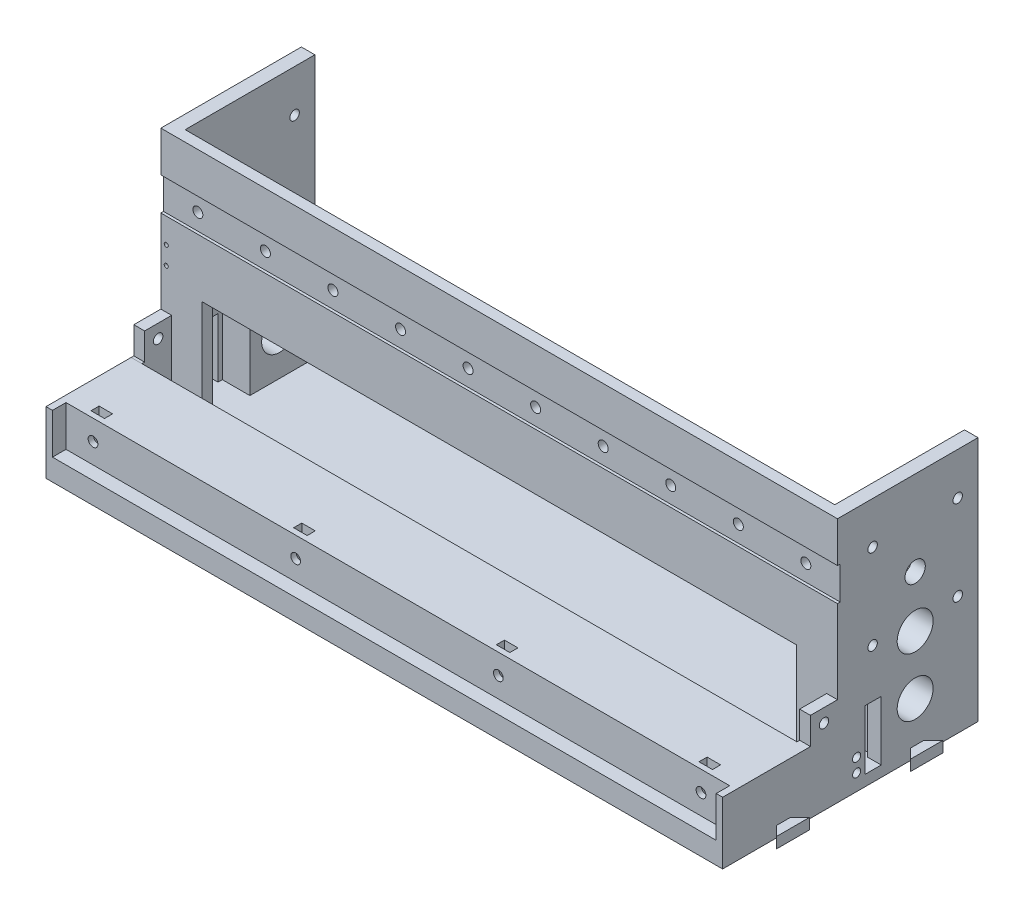
SolidWorks part; units mm, degrees
ref_plane "Front Plane" through (0, 0, 0) normal (0, 0, 1) x (1, 0, 0)
ref_plane "Top Plane" through (0, 0, 0) normal (0, 1, 0) x (1, 0, 0)
ref_plane "Right Plane" through (0, 0, 0) normal (1, 0, 0) x (0, 0, -1)
sketch "Sketch21" plane through (0, 0, 0) normal (0, 1, 0) x (1, 0, 0)
  line L1 (0, 0) -> (250.4, 0)
  line L2 (0, 0) -> (0, -94.5)
  line L3 (0, -94.5) -> (250.4, -94.5)
  line L4 (250.4, 0) -> (250.4, -94.5)
  dimension "D1" = 250.4
  dimension "D2" = 94.5
extrude "Base" add sketch "Sketch21" along normal blind 4
sketch "Sketch22" plane through (0, 4, 0) normal (0, 1, 0) x (1, 0, 0)
  line L1 (0, -52) -> (250.4, -52)
  line L2 (0, -52) -> (0, -48)
  line L3 (0, -48) -> (250.4, -48)
  line L4 (250.4, -52) -> (250.4, -48)
  line L7 (250.4, 0) -> (0, 0) construction
  dimension "D1" = 4
  dimension "D2" = 48
extrude "MainWall" add sketch "Sketch22" along normal blind 87
ref_plane "MiddlePlane" through (125.2, 0, 0) normal (-1, 0, 0) x (0, 0, 1)
sketch "Sketch2" plane through (0, 0, 52) normal (0, 0, 1) x (1, 0, 0)
  line L0 (0, 91) -> (0, 4) construction
  line L1 (250.4, 76) -> (0, 76)
  line L2 (250.4, 76) -> (250.4, 63.8)
  line L3 (250.4, 63.8) -> (0, 63.8)
  line L4 (0, 76) -> (0, 63.8)
  line L5 (0, 91) -> (250.4, 91) construction
  line L6 (250.4, 91) -> (250.4, 4) construction
  dimension "D1" = 12.2
  dimension "D3" = 15
extrude "RailCutout" cut sketch "Sketch2" against normal blind 1
sketch "Sketch6" plane through (0, 0, 52) normal (0, 0, 1) x (1, 0, 0)
  line L0 (0, 63.8) -> (250.4, 63.8) construction
  line L1 (235.2, 23) -> (15.2, 23)
  line L2 (235.2, 23) -> (235.2, 43)
  line L3 (235.2, 43) -> (15.2, 43)
  line L5 (125.2, 63.8) -> (125.2, 43) construction
  line L6 (0, 4) -> (250.4, 4) construction
  line L9 (15.2, 43) -> (15.2, 23)
  dimension "D1" = 20
  dimension "D2" = 19
  dimension "D3" = 220
extrude "PaperChannel" cut sketch "Sketch6" against normal blind 5
sketch "Sketch3" plane through (0, 0, 51) normal (0, 0, 1) x (1, 0, 0)
  line L1 (250.4, 63.8) -> (250.4, 76) construction
  line L3 (237.7, 69.9) -> (250.4, 69.9) construction
  circle A0 centre (237.7, 69.9) radius 1.85
  dimension "D1" = 12.7
  dimension "D2" = 3.7
extrude "RailScrewHole" cut sketch "Sketch3" against normal blind 4
pattern_linear "RailScrewPattern" count 10 spacing 25 along (-1, 0, 0) of "RailScrewHole"
sketch "Sketch13" plane through (0, 0, 0) normal (1, 0, 0) x (0, 0, -1)
  line L0 (0, 4) -> (0, 0) construction
  line L1 (-48, 91) -> (0, 91)
  line L2 (-48, 91) -> (-48, 4)
  line L3 (-48, 4) -> (0, 4)
  line L4 (0, 91) -> (0, 4)
  line L6 (-48, 91) -> (-48, 4) construction
  line L7 (0, 4) -> (-48, 4) construction
  dimension "D2" = 87
extrude "YWall" add sketch "Sketch13" along normal blind 5
sketch "Sketch20" plane through (0, 4, 0) normal (0, 1, 0) x (1, 0, 0)
  line L0 (250.4, -94.5) -> (250.4, -52) construction
  line L1 (250.4, -52) -> (0, -52)
  line L2 (250.4, -52) -> (250.4, -94.5)
  line L3 (250.4, -94.5) -> (0, -94.5)
  line L4 (0, -52) -> (0, -94.5)
  line L5 (0, -52) -> (0, -94.5) construction
  line L8 (0, -52) -> (250.4, -52) construction
  dimension "D2" = 42.5
extrude "BaseExtension" add sketch "Sketch20" along normal blind 19
sketch "Sketch14" plane through (0, 0, 0) normal (1, 0, 0) x (0, 0, -1)
  line L0 (-23.25, 40.65) -> (-23.25, 19) construction
  line L1 (-48, 4) -> (0, 4) construction
  line L2 (-23.25, 40.65) -> (-23.25, 59.65) construction
  line L3 (-39, 75.4) -> (-7.5, 75.4) construction
  line L4 (-39, 75.4) -> (-7.5, 43.9) construction
  line L5 (-7.5, 75.4) -> (-39, 43.9) construction
  line L6 (-39, 43.9) -> (-7.5, 43.9) construction
  line L7 (-48, 91) -> (-48, 4) construction
  circle A0 centre (-23.25, 19) radius 6.65
  circle A1 centre (-23.25, 40.65) radius 6.65
  circle A2 centre (-23.25, 59.65) radius 3.75
  circle A3 centre (-7.5, 43.9) radius 1.75
  circle A4 centre (-7.5, 75.4) radius 1.75
  circle A5 centre (-39, 75.4) radius 1.75
  circle A6 centre (-39, 43.9) radius 1.75
  point P18 (-23.25, 59.65)
  dimension "D1" = 21.65
  dimension "D2" = 13.3
  dimension "D3" = 13.3
  dimension "D6" = 7.5
  dimension "D7" = 3.5
  dimension "D8" = 3.5
  dimension "D9" = 3.5
  dimension "D10" = 3.5
  dimension "D15" = 15
  dimension "D4" = 9
  dimension "D5" = 19
  dimension "D11" = 31.5
  dimension "D12" = 31.5
  dimension "D13" = 31.5
  dimension "D14" = 31.5
extrude "MotorScrewBearingHoles" cut sketch "Sketch14" along normal blind 5
mirror "MirrorYWallHoles" about plane through (125.2, 0, 0) normal (-1, 0, 0) of "MotorScrewBearingHoles", "YWall"
sketch "Sketch26" plane through (5, 0, 0) normal (1, 0, 0) x (0, 0, -1)
  line L0 (-23.25, 50.65) -> (-23.25, 4) construction
  line L1 (-34.25, 4) -> (-12.25, 4)
  line L2 (-34.25, 4) -> (-34.25, 43.15)
  line L3 (-26.75, 50.65) -> (-19.75, 50.65)
  line L4 (-12.25, 4) -> (-12.25, 43.15)
  line L6 (-48, 4) -> (0, 4) construction
  circle A0 centre (-23.25, 19) radius 6.65
  circle A1 centre (-23.25, 40.65) radius 6.65
  arc A2 (-34.25, 43.15) -> (-26.75, 50.65) centre (-26.75, 43.15) cw
  arc A3 (-19.75, 50.65) -> (-12.25, 43.15) centre (-19.75, 43.15) cw
  dimension "D1" = 10
  dimension "D2" = 7.5
  dimension "D3" = 22
extrude "LeftRollerOffset" add sketch "Sketch26" along normal blind 10.2
chamfer "Chamfer2" distance 15 angle 45 1 edges at (125.2, 23, 48)
sketch "Sketch28" plane through (245.4, 0, 0) normal (-1, 0, 0) x (0, 0, 1)
  line L0 (48, 4) -> (0, 4) construction
  line L1 (19.75, 50.65) -> (26.75, 50.65)
  line L2 (12.25, 43.15) -> (12.25, 4)
  line L3 (12.25, 4) -> (34.25, 4)
  line L4 (34.25, 43.15) -> (34.25, 4)
  line L5 (23.25, 4) -> (23.25, 50.65) construction
  circle A0 centre (23.25, 40.65) radius 6.65
  circle A2 centre (23.25, 19) radius 6.65
  arc A3 (19.75, 50.65) -> (12.25, 43.15) centre (19.75, 43.15) ccw
  arc A4 (26.75, 50.65) -> (34.25, 43.15) centre (26.75, 43.15) cw
  dimension "D1" = 10
  dimension "D3" = 7.5
  dimension "D2" = 22
extrude "RightRollerOffset" add sketch "Sketch28" along normal blind 10
sketch "Sketch29" plane through (0, 0, 0) normal (-1, 0, 0) x (0, 0, 1)
  line L0 (52, 23) -> (52, 33)
  line L1 (52, 63.8) -> (52, 12) construction
  line L3 (63, 23) -> (94.5, 23) construction
  line L5 (52, 33) -> (62, 33)
  line L6 (62, 33) -> (62, 23)
  line L7 (52, 33) -> (62, 23) construction
  line L8 (52, 23) -> (52, 12)
  line L9 (52, 12) -> (63, 23)
  line L10 (63, 23) -> (62, 23)
  line L11 (62, 23) -> (52, 23) construction
  circle A0 centre (57, 28) radius 1.75
  point P10 (57, 28)
  dimension "D3" = 3.5
  dimension "D1" = 10
  dimension "D2" = 10
extrude "BackMountScrew" add sketch "Sketch29" against normal blind 4 separate body
mirror "Mirror5" about plane through (125.2, 0, 0) normal (-1, 0, 0) of "BackMountScrew"
sketch "Sketch34" plane through (0, 0, 0) normal (0, -1, 0) x (1, 0, 0)
  line L0 (0, 64.75) -> (-3.5355, 68.2855)
  line L1 (0, 0) -> (0, 94.5) construction
  line L2 (-3.5355, 68.2855) -> (-3.5355, 56.2145)
  line L3 (-3.5355, 56.2145) -> (0, 59.75)
  line L4 (0, 59.75) -> (0, 64.75)
  line L5 (0, 47.25) -> (0, 62.25) construction
  line L6 (0, 47.25) -> (250.4, 47.25) construction
  line L7 (250.4, 94.5) -> (250.4, 0) construction
  line L9 (-3.5355, 38.2855) -> (0, 34.75)
  line L10 (-3.5355, 26.2145) -> (-3.5355, 38.2855)
  line L11 (0, 29.75) -> (-3.5355, 26.2145)
  line L12 (0, 34.75) -> (0, 29.75)
  dimension "D1" = 45
  dimension "D2" = 5
  dimension "D3" = 5
  dimension "D4" = 15
extrude "Dovetails_Left" add sketch "Sketch34" against normal blind 4
sketch "Sketch49" plane through (0, 0, 0) normal (0, -1, 0) x (1, 0, 0)
  line L0 (250.4, 74.5) -> (253.9355, 78.0355)
  line L1 (250.4, 94.5) -> (250.4, 0) construction
  line L2 (253.9355, 78.0355) -> (253.9355, 65.9645)
  line L3 (253.9355, 65.9645) -> (250.4, 69.5)
  line L4 (250.4, 69.5) -> (250.4, 74.5)
  line L5 (250.4, 47.25) -> (0, 47.25) construction
  line L6 (0, 0) -> (0, 94.5) construction
  line L7 (250.4, 25) -> (250.4, 20)
  line L8 (253.9355, 28.5355) -> (250.4, 25)
  line L9 (253.9355, 16.4645) -> (253.9355, 28.5355)
  line L10 (250.4, 20) -> (253.9355, 16.4645)
  dimension "D1" = 20
  dimension "D2" = 5
  dimension "D3" = 5
  dimension "D4" = 45
extrude "Dovetails_Right" add sketch "Sketch49" against normal blind 4
sketch "Sketch43" plane through (0, 0, 52) normal (0, 0, 1) x (1, 0, 0)
  line L0 (0, 91) -> (250.4, 91) construction
  line L1 (0, 63.8) -> (0, 12) construction
  circle A0 centre (2, 54.6) radius 0.75
  circle A1 centre (2, 47.9) radius 0.75
  dimension "D1" = 1.5
  dimension "D3" = 1.5
  dimension "D2" = 36.4
  dimension "D4" = 6.7
  dimension "D5" = 2
extrude "Endstop_Screw_Holes" cut sketch "Sketch43" against normal blind 4
sketch "Sketch44" plane through (5, 0, 0) normal (1, 0, 0) x (0, 0, -1)
  line L1 (-48, 4) -> (-34.25, 4) construction
  line L6 (-43.4167, 6) -> (-34.25, 6) construction
  line L7 (-41.8333, 4) -> (-35.8333, 4)
  line L8 (-41.8333, 4) -> (-41.8333, 26)
  line L9 (-41.8333, 26) -> (-35.8333, 26)
  line L10 (-35.8333, 4) -> (-35.8333, 26)
  line L11 (-44.9167, 11) -> (-41.8333, 11) construction
  line L12 (-44.9167, 11) -> (-48, 11) construction
  line L13 (-48, 91) -> (-48, 4) construction
  line L14 (-44.9167, 11) -> (-44.9167, 6) construction
  line L15 (-34.25, 43.15) -> (-34.25, 4) construction
  line L16 (-38.8333, 6) -> (-38.8333, 4) construction
  circle A0 centre (-44.9167, 11) radius 1.5
  circle A1 centre (-44.9167, 6) radius 1.5
  dimension "D3" = 3
  dimension "D4" = 3
  dimension "D1" = 22
  dimension "D2" = 6
  dimension "D5" = 5
  dimension "D6" = 2
extrude "Cable_Passthrough" cut sketch "Sketch44" against normal up to next (5 mm away)
mirror "Cabble_Passthrough_Mirror" about plane through (125.2, 0, 0) normal (-1, 0, 0) of "Cable_Passthrough"
sketch "Sketch46" plane through (0, 23, 0) normal (0, 1, 0) x (1, 0, 0)
  line L0 (0, -94.5) -> (250.4, -94.5) construction
  line L1 (2.4, -89.5) -> (248, -89.5)
  line L2 (2.4, -89.5) -> (2.4, -94.5)
  line L3 (2.4, -94.5) -> (248, -94.5)
  line L4 (248, -89.5) -> (248, -94.5)
  line L5 (125.2, 50.05) -> (125.2, -50.05) construction
  point P6 (125.2, -94.5)
  dimension "D1" = 5
  dimension "D2" = 245.6
extrude "Channel_Cutout" cut sketch "Sketch46" against normal blind 15
sketch "Sketch47" plane through (0, 0, 89.5) normal (0, 0, 1) x (1, 0, 0)
  line L1 (2.4, 8) -> (2.4, 23) construction
  line L2 (248, 23) -> (2.4, 23) construction
  circle A0 centre (12.4, 15.5) radius 1.8
  dimension "D1" = 3.6
  dimension "D2" = 10
  dimension "D3" = 7.5
extrude "Channel_Screw_Hole" cut sketch "Sketch47" against normal blind 4
sketch "Sketch48" plane through (0, 23, 0) normal (0, 1, 0) x (1, 0, 0)
  line L0 (2.4, -89.5) -> (2.4, -94.5) construction
  line L1 (9.65, -84.5) -> (14.65, -84.5)
  line L2 (9.65, -84.5) -> (9.65, -87.5)
  line L3 (9.65, -87.5) -> (14.65, -87.5)
  line L4 (14.65, -84.5) -> (14.65, -87.5)
  line L5 (248, -89.5) -> (2.4, -89.5) construction
  dimension "D1" = 3
  dimension "D2" = 5
  dimension "D3" = 7.25
  dimension "D4" = 2
extrude "Channel_Nut_Hole" cut sketch "Sketch48" against normal blind 11.3
pattern_linear "LPattern1" count 4 spacing 75 along (1, 0, 0) of "Channel_Screw_Hole", "Channel_Nut_Hole"
equation "\"45.5.00mm\"=10"
equation "\"14.5.00mm\"=15"
